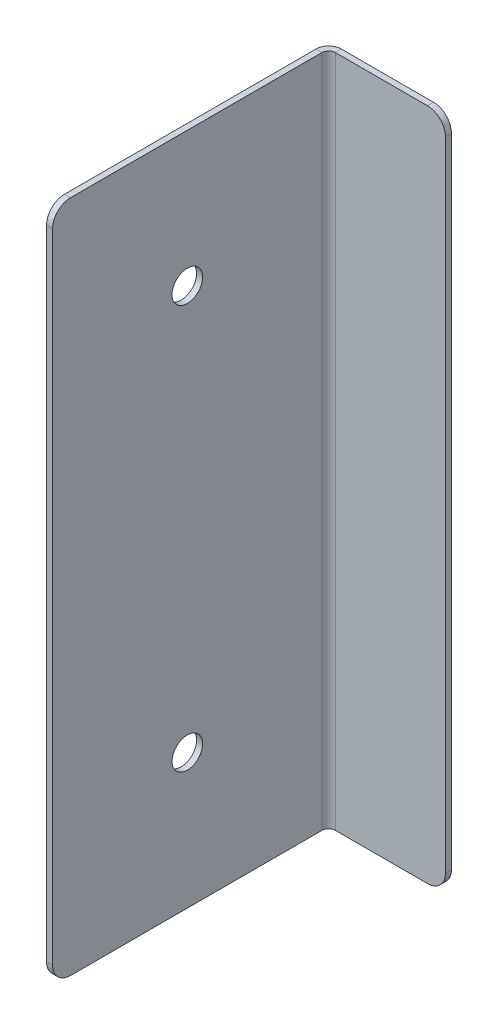
SolidWorks part; units mm, degrees
note: The reader was unsure of these and kept them because the rebuilt part matched: flange length of "Edge-Flange1".
material "Plain Carbon Steel"
ref_plane "Front Plane" through (0, 0, 0) normal (0, 0, 1) x (1, 0, 0)
ref_plane "Top Plane" through (0, 0, 0) normal (0, 1, 0) x (1, 0, 0)
ref_plane "Right Plane" through (0, 0, 0) normal (1, 0, 0) x (0, 0, -1)
sketch "Sketch1" plane through (0, 0, 0) normal (1, 0, 0) x (0, 0, -1)
  line L1 (0, 0) -> (30, 0)
  line L2 (0, 0) -> (0, -75)
  line L3 (0, -75) -> (30, -75)
  line L4 (30, 0) -> (30, -75)
  dimension "D1" = 75
  dimension "D2" = 30
sheet metal parameters "Sheet-Metal1" thickness 0.67 parameters "D1"=0.7366
base flange "Base-Flange1" sketch "Sketch1" thickness 0.67 reverse thickness direction no parameters "D1"=0.7366
edge flange "Edge-Flange1" sketch "Sketch9" flange angle 90 flange length 13 flange position bend outside bend radius 0.7366 thickness 0.67 relief rectangular parameters "D6"=10
bend "EdgeBend2" bend radius 0.7366 bend angle 90 parameters "D5"=1
sketch "Sketch9" plane through (0, 0, -30) normal (0, 0, -1) x (0, 1, 0)
  line L0 (-75, 0) -> (0, 0) construction
  line L1 (-75, 0) -> (0, 0)
  line L2 (-75, 0) -> (-75, 13)
  line L3 (-75, 13) -> (0, 13)
  line L4 (0, 13) -> (0, 0)
  line L5 (0, -0.67) -> (0, 0) construction
  dimension "D2" = 13
sketch "Sketch7" plane through (0, 0, 0) normal (1, 0, 0) x (0, 0, -1)
  line L0 (15, -75) -> (15, 0) construction
  line L1 (0, -75) -> (30, -75) construction
  line L2 (30, 0) -> (0, 0) construction
  circle A0 centre (15, -60) radius 1.7
  circle A1 centre (15, -15) radius 1.7
  dimension "D1" = 3.4
  dimension "D2" = 3.4
  dimension "D3" = 15
  dimension "D4" = 15
extrude "Cut-Extrude1" cut sketch "Sketch7" against normal blind 10 normal cut yes
fillet "Fillet1" radius 2 4 edges at (-0.335, 0, 0) (13, 0, -31.0716) (13, -75, -31.0716) (-0.335, -75, 0)
flat pattern "Flat-Pattern1" [suppressed]
sketch "Bend-Lines1" plane through (0, 0, 0) normal (1, 0, 0) x (0, 0, -1)
  line L0 (30.8416, -75) -> (30.8416, 0) construction
  line L1 (30.8416, -75) -> (30.8416, 0) construction
  point P1 (30.8416, 0)
sketch3d "Bounding-Box1" [suppressed]
  line L0 (43.9466, -75, 0) -> (43.9467, 0, 0) construction
  line L1 (0, -75, 0) -> (0, 0, 0) construction
  line L2 (43.9466, -75, 0) -> (0, -75, 0) construction
  line L3 (43.9467, 0, 0) -> (0, 0, 0) construction
bend of the flat pattern "Flatten-<EdgeBend2>1"
